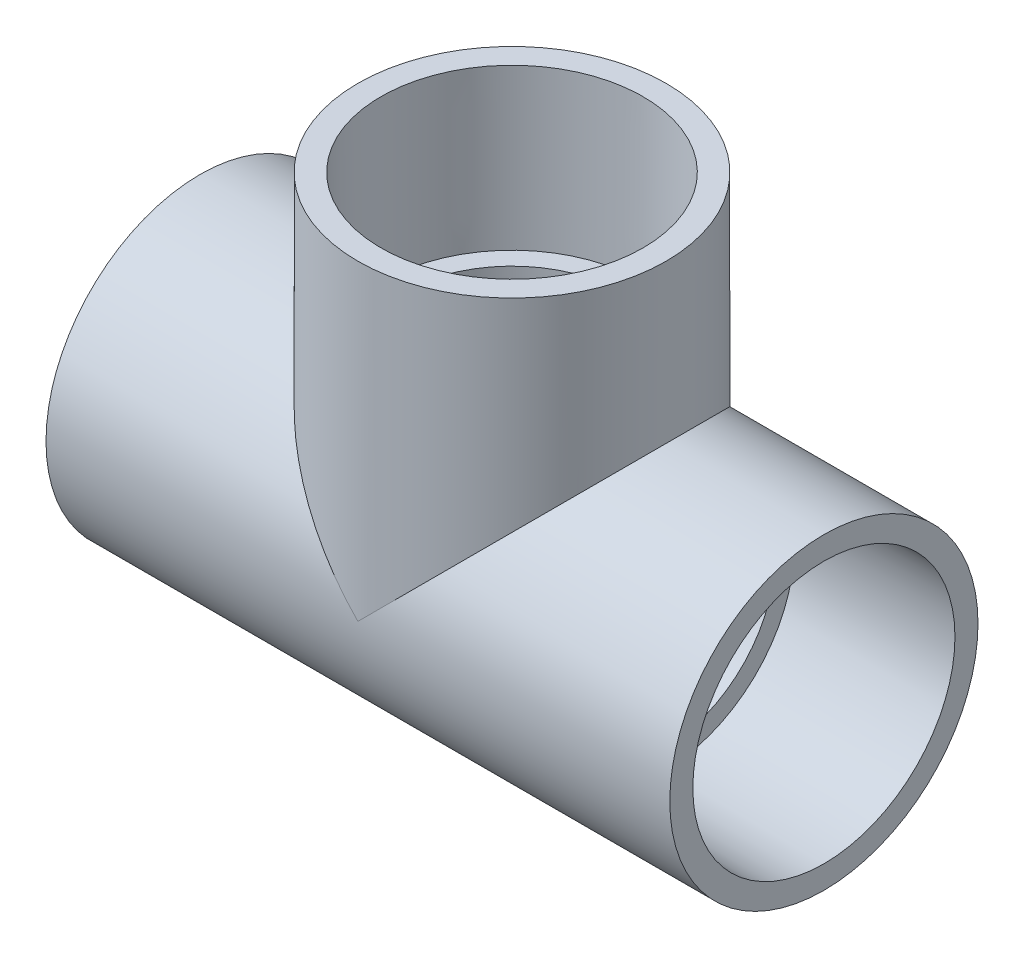
SolidWorks part; units mm, degrees
ref_plane "Front Plane" through (0, 0, 0) normal (0, 0, 1) x (1, 0, 0)
ref_plane "Top Plane" through (0, 0, 0) normal (0, 1, 0) x (1, 0, 0)
ref_plane "Right Plane" through (0, 0, 0) normal (1, 0, 0) x (0, 0, -1)
sketch "Sketch0" plane through (0, 0, 0) normal (0, 0, 1) x (1, 0, 0)
  line L0 (-57.785, 0) -> (0, 0) construction
  line L1 (0, 0) -> (0, 57.785) construction
  line L2 (-28.2702, 0) -> (0, 0) construction
  line L3 (0, 0) -> (0, 28.2702) construction
  line L4 (-57.785, 28.5496) -> (-57.785, -28.5496) construction
  line L5 (-28.2702, 24.0538) -> (-57.785, 24.2824) construction
  line L6 (-28.2702, 24.0538) -> (-28.2702, -24.0538) construction
  line L7 (-28.2702, -24.0538) -> (-57.785, -24.2824) construction
  line L8 (-57.785, 24.2824) -> (-57.785, -24.2824) construction
  line L9 (-28.5496, 57.785) -> (28.5496, 57.785) construction
  line L10 (-24.2824, 57.785) -> (24.2824, 57.785) construction
  line L11 (24.2824, 57.785) -> (24.0538, 28.2702) construction
  line L12 (24.0538, 28.2702) -> (-24.0538, 28.2702) construction
  line L13 (-24.0538, 28.2702) -> (-24.2824, 57.785) construction
  line L14 (-28.2702, 20.447) -> (-28.2702, -20.447) construction
  line L15 (-57.785, 0) -> (-28.2702, 0) construction
  line L16 (0, 57.785) -> (0, 28.2702) construction
  line L17 (0, 0) -> (28.2702, 0) construction
  line L18 (-20.447, 28.2702) -> (20.447, 28.2702) construction
  line L19 (28.2702, 0) -> (57.785, 0) construction
  dimension "A" = 57.785
  dimension "B" = 28.2702
  dimension "D" = 57.0992
  dimension "OD A" = 48.5648
  dimension "OD B" = 48.1076
  dimension "ID" = 40.894
  dimension "A3" = 57.785
  dimension "D3" = 57.0992
  dimension "C" = 29.5148
  dimension "B3" = 28.2702
  dimension "C3" = 29.5148
sketch "Sketch1" plane through (0, 0, 0) normal (0, 0, 1) x (1, 0, 0)
  line L0 (-57.785, 0) -> (0, 0) construction
  line L1 (-57.785, 0) -> (0, 0) construction
  line L2 (0, 0) -> (0, -28.5496) construction
  line L3 (-57.785, -28.5496) -> (-28.2702, -28.5496)
  line L4 (-57.785, -28.5496) -> (-57.785, -24.2824)
  line L5 (-57.785, -24.2824) -> (-28.2702, -24.0538)
  line L6 (-28.2702, -28.5496) -> (-28.2702, -24.0538)
  line L7 (-28.2702, -28.5496) -> (0, -28.5496) construction
  line L8 (57.785, -24.2824) -> (28.2702, -24.0538)
  line L9 (57.785, -28.5496) -> (57.785, -24.2824)
  line L10 (28.2702, -28.5496) -> (28.2702, -24.0538)
  line L11 (57.785, -28.5496) -> (28.2702, -28.5496)
revolve "Revolve1" add sketch "Sketch1" angle 360 about L1
sketch "Sketch2" plane through (0, 0, 0) normal (0, 0, 1) x (1, 0, 0)
  line L0 (24.2824, 57.785) -> (24.0538, 28.2702)
  line L1 (24.0538, 28.2702) -> (28.5496, 28.2702)
  line L2 (28.5496, 28.2702) -> (28.5496, 57.785)
  line L3 (28.5496, 57.785) -> (24.2824, 57.785)
  line L4 (0, 0) -> (0, 57.785) construction
  line L5 (0, 0) -> (0, 57.785) construction
revolve "Revolve2" add sketch "Sketch2" angle 360 about L5
sketch "Sketch3" plane through (-28.2702, 0, 0) normal (1, 0, 0) x (0, 0, -1)
  circle A0 centre (0, 0) radius 28.5496 construction
  circle A1 centre (0, 0) radius 28.5496
extrude "Boss-Extrude1" add sketch "Sketch3" along normal up to vertex (56.5404 mm away) up to point (28.2702, 0, 0)
sketch "Sketch4" plane through (0, 28.2702, 0) normal (0, -1, 0) x (1, 0, 0)
  circle A0 centre (0, 0) radius 28.5496 construction
  circle A1 centre (0, 0) radius 28.5496
extrude "Boss-Extrude2" add sketch "Sketch4" along normal up to vertex (28.2702 mm away) up to point (0, 0, 0)
sketch "Sketch5" plane through (0, 0, 0) normal (0, 0, 1) x (1, 0, 0)
  line L0 (-57.785, -24.2824) -> (-28.2702, -24.0538)
  line L1 (-28.2702, -24.0538) -> (-28.2702, -20.447)
  line L2 (-28.2702, -20.447) -> (28.2702, -20.447)
  line L3 (28.2702, -24.0538) -> (28.2702, 23.7215) construction
  line L4 (0, -20.447) -> (0, 0) construction
  line L5 (28.2702, -24.0538) -> (28.2702, -20.447)
  line L6 (57.785, -24.2824) -> (57.785, 24.2824) construction
  line L7 (57.785, -28.5496) -> (57.785, 28.5496) construction
  line L8 (57.785, -24.2824) -> (57.785, 0)
  line L9 (57.785, 0) -> (-57.785, 0)
  line L10 (-57.785, 0) -> (-57.785, -24.2824)
  line L11 (57.785, -24.2824) -> (28.2702, -24.0538)
revolve "Cut-Revolve1" cut sketch "Sketch5" angle 360 about L9
sketch "Sketch6" plane through (0, 0, 0) normal (0, 0, 1) x (1, 0, 0)
  line L0 (24.2824, 57.785) -> (24.0538, 28.2702)
  line L1 (24.0538, 28.2702) -> (20.447, 28.2702)
  line L2 (20.447, 28.2702) -> (20.447, 0)
  line L3 (0, 0) -> (28.2702, 0) construction
  line L4 (20.447, 0) -> (0, 0)
  line L5 (0, 0) -> (0, 57.785)
  line L6 (-28.5496, 57.785) -> (28.5496, 57.785) construction
  line L7 (0, 57.785) -> (24.2824, 57.785)
revolve "Cut-Revolve2" cut sketch "Sketch6" angle 360 about L5
other "CPoint1" parameters "Diameter"=38.1, "StubLength"=57.15
ref_axis "Axis1" through (-38.2702, 0, 0) along (1, 0, 0)
other "CPoint2" parameters "Diameter"=38.1, "StubLength"=57.15
ref_axis "Axis2" through (38.2702, 0, 0) along (-1, 0, 0)
other "CPoint3" parameters "Diameter"=38.1, "StubLength"=57.15
ref_axis "Axis3" through (0, 38.2702, 0) along (0, -1, 0)
other "RPoint1"
